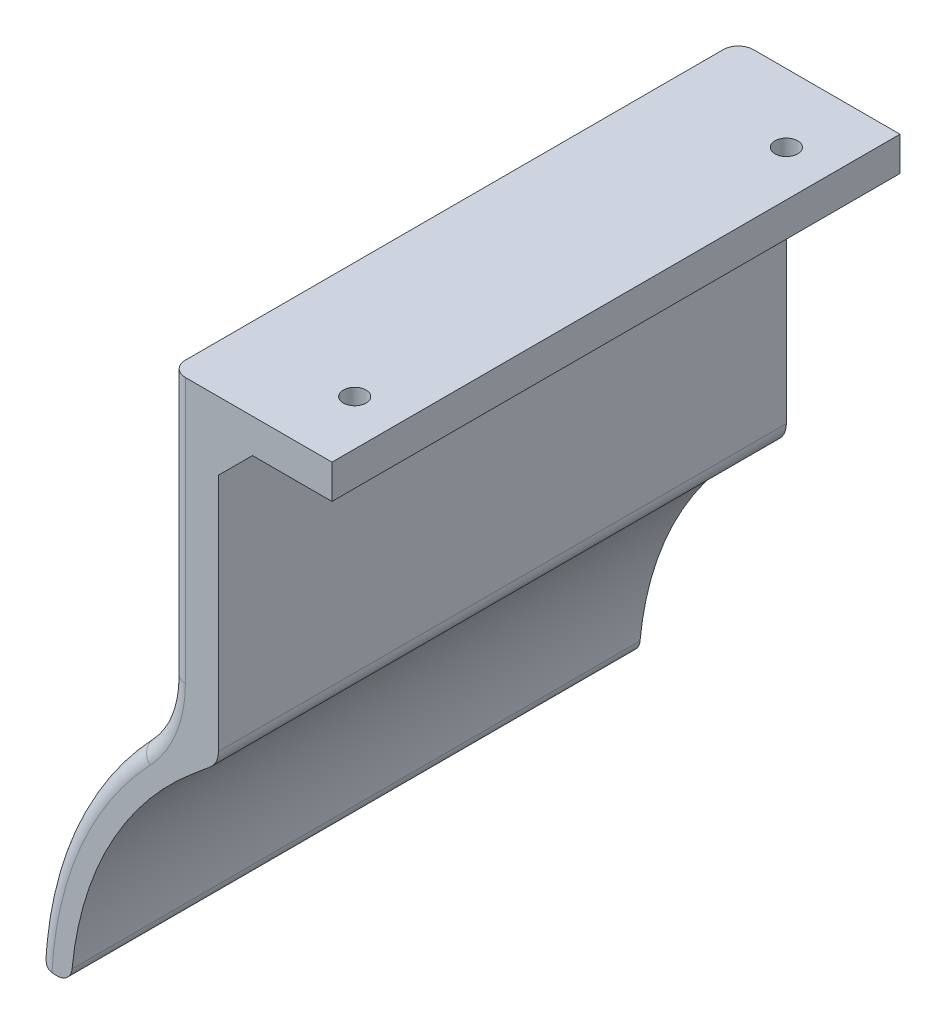
SolidWorks part; units mm, degrees
ref_plane "前视基准面" through (0, 0, 0) normal (0, 0, 1) x (1, 0, 0)
ref_plane "上视基准面" through (0, 0, 0) normal (0, 1, 0) x (1, 0, 0)
ref_plane "右视基准面" through (0, 0, 0) normal (1, 0, 0) x (0, 0, -1)
other "Configuration Table"
sketch "草图1" plane through (0, 0, 0) normal (0, 0, 1) x (1, 0, 0)
  line L1 (-30, 0) -> (0, 0) construction
  line L4 (-30, 0) -> (-33, 0)
  line L6 (0, 33) -> (-44.8073, 33) construction
  line L7 (-19.2836, 22.9813) -> (-16.9855, 24.9097)
  line L8 (-16.9855, 24.9097) -> (-16.9855, 39.9097)
  line L9 (-21.212, 25.2795) -> (-21.212, 39.9097)
  line L10 (-21.212, 39.9097) -> (-28.212, 39.9097)
  line L11 (-28.212, 39.9097) -> (-28.212, 42.9097)
  line L12 (-28.212, 42.9097) -> (-16.9855, 42.9097)
  line L13 (-16.9855, 42.9097) -> (-16.9855, 39.9097)
  line L14 (-21.212, 25.2795) -> (-16.9855, 24.9097)
  arc A0 (-30, 0) -> (-19.2836, 22.9813) centre (0, 0) cw
  arc A1 (-33, 0) -> (-21.212, 25.2795) centre (0, 0) cw
  arc A2 (-19.2836, 22.9813) -> (0, 30) centre (0, 0) cw construction
  arc A3 (-21.212, 25.2795) -> (0, 33) centre (0, 0) cw construction
  dimension "D1" = 30
  dimension "D4" = 33
  dimension "D6" = 50
  dimension "D2" = 50
  dimension "D3" = 3
  dimension "D5" = 3
  dimension "D7" = 15
  dimension "D8" = 7
  dimension "D9" = 3
extrude "凸台-拉伸1" add sketch "草图1" along normal mid plane 50 contours A1 L4 A0 L7 L14 region at (-27.2319, 13.4982, 0)
extrude "凸台-拉伸3" add sketch "草图1<7>" along normal mid plane 50 contours L9 L14 L8 L13 L12 L11 L10 region at (-20.3172, 35.6173, 0)
sketch "草图1<7>" plane through (0, 0, 0) normal (0, 0, 1) x (1, 0, 0) same geometry as "草图1"
ref_plane "基准面6" through (-16.9855, 0, 0) normal (1, 0, 0) x (0, 0, -1)
sketch "草图4" plane through (-16.9855, 0, 0) normal (1, 0, 0) x (0, 0, -1)
  line L0 (-25, 24.9097) -> (-16, 24.9097) construction
  line L1 (-25, 24.9097) -> (25, 24.9097) construction
  line L2 (25, 24.9097) -> (16, 24.9097) construction
  line L8 (-25, 42.9097) -> (25, 42.9097) construction
  line L9 (-16, 42.9097) -> (16, 42.9097)
  line L10 (-16, 42.9097) -> (-16, 27.9969)
  line L11 (-16, 27.9969) -> (16, 27.9969)
  line L12 (16, 42.9097) -> (16, 27.9969)
extrude "切除-拉伸1" cut sketch "草图4" against normal through all and the other way through all
fillet "圆角1" radius 10 1 edges at (-21.212, 25.2795, 0)
fillet "圆角17" radius 2 1 edges at (-16.9855, 24.9097, 0) type face fillet first side face at (-16.9855, 34.6815, 0) second side face at (-18.1346, 23.9455, 0)
sketch "草图5" plane through (0, 0, 0) normal (1, 0, 0) x (0, 0, -1)
  line L0 (-25, 0) -> (25, 0) construction
  line L3 (0, 0) -> (0, 22.9813) construction
  line L4 (-14, 9) -> (14, 9)
  line L5 (-14, 9) -> (-14, 16.4661)
  line L6 (-14, 16.4661) -> (14, 16.4661)
  line L7 (14, 9) -> (14, 16.4661)
  line L8 (-25, 22.9813) -> (25, 22.9813) construction
  line L9 (-25, 22.9813) -> (-25, 0) construction
  dimension "D1" = 28
  dimension "D2" = 16.4661
  dimension "D3" = 11
  dimension "D4" = 9
sketch "草图7" plane through (0, 0, 0) normal (0, 0, 1) x (1, 0, 0)
  line L0 (0, 0) -> (-33, 0)
  line L1 (-32.9548, 1.7271) -> (0, 0)
  arc A0 (-33, 0) -> (-32.9548, 1.7271) centre (0, 0) cw
  dimension "D1" = 3
extrude "切除-拉伸5" cut sketch "草图7" against normal through all both and the other way through all
sketch "草图9" plane through (0, 0, 0) normal (0, 0, 1) x (1, 0, 0)
  line L1 (-21.212, 39.9097) -> (-28.212, 39.9097)
  line L2 (-21.212, 39.9097) -> (-21.212, 42.9097)
  line L3 (-21.212, 42.9097) -> (-28.212, 42.9097)
  line L4 (-28.212, 39.9097) -> (-28.212, 42.9097)
extrude "切除-拉伸6" cut sketch "草图9" against normal through all both and the other way through all
ref_plane "基准面7" through (0, 42.9097, 0) normal (0, 1, 0) x (1, 0, 0)
sketch "草图10" plane through (0, 42.9097, 0) normal (0, 1, 0) x (1, 0, 0)
  line L0 (-16.9855, -13.2371) -> (-16.9855, 13.2371) construction
  line L1 (-21.212, 25) -> (-16.9855, 25)
  line L2 (-21.212, 25) -> (-21.212, 16)
  line L3 (-21.212, 16) -> (-16.9855, 16)
  line L4 (-16.9855, 25) -> (-16.9855, 16)
  line L5 (-21.212, 16) -> (-16.9855, 16) construction
  line L6 (-21.212, -25) -> (-16.9855, -25) construction
  line L7 (-21.212, -16) -> (-16.9855, -16)
  line L8 (-21.212, -16) -> (-21.212, -25)
  line L9 (-21.212, -25) -> (-16.9855, -25)
  line L10 (-16.9855, -16) -> (-16.9855, -25)
extrude "凸台-拉伸4" add sketch "草图10" along normal blind 10
sketch "草图12" plane through (-16.9855, 0, 0) normal (1, 0, 0) x (0, 0, -1)
  line L0 (25, 25.8423) -> (25, 52.9097) construction
  line L1 (-25, 52.9097) -> (25, 52.9097)
  line L2 (-25, 52.9097) -> (-25, 49.9097)
  line L3 (-25, 49.9097) -> (25, 49.9097)
  line L4 (25, 52.9097) -> (25, 49.9097)
  dimension "D1" = 3
extrude "凸台-拉伸6" add sketch "草图12" along normal blind 10 and the other way up to surface (4.2265 mm away) other way up to face at (-21.212, 41.2435, 20.5)
ref_plane "基准面8" through (0, 49.9097, 0) normal (0, -1, 0) x (-1, 0, 0)
sketch "草图14" plane through (0, 49.9097, 0) normal (0, -1, 0) x (-1, 0, 0)
  line L0 (6.9855, 25) -> (6.9855, 19) construction
  line L1 (6.9855, -25) -> (6.9855, 25) construction
  line L3 (6.9855, 19) -> (10.9855, 19) construction
  circle A0 centre (10.9855, 19) radius 1
  circle A1 centre (10.9855, -19) radius 1
  dimension "D3" = 2
  dimension "D1" = 6
  dimension "D2" = 4
extrude "切除-拉伸8" cut sketch "草图14" against normal through all
fillet "圆角50" radius 1.32 8 edges at (-30.3247, 13.0158, -25) (-21.9226, 25.8749, -25) (-30.3247, 13.0158, 25) (-21.9226, 25.8749, 25) (-21.212, 41.2435, -25) (-21.212, 41.2435, 25) (-29.9589, 1.5701, 0) (-32.9548, 1.7271, 0)
sketch "草图16" plane through (-16.9855, 0, 0) normal (1, 0, 0) x (0, 0, -1)
  line L1 (-16, 27.9969) -> (16, 27.9969)
  line L2 (-16, 27.9969) -> (-16, 49.9097)
  line L3 (-16, 49.9097) -> (16, 49.9097)
  line L4 (16, 27.9969) -> (16, 49.9097)
extrude "凸台-拉伸7" add sketch "草图16" against normal up to surface (4.2265 mm away) up to face at (-21.212, 40.4935, 0)
sketch "草图17" plane through (0, 0, -16) normal (0, 0, 1) x (1, 0, 0)
  line L2 (-21.3376, 27.9969) -> (-21.212, 27.9969)
  line L3 (-21.212, 27.9969) -> (-21.212, 29.5772)
  line L4 (-21.3376, 27.9969) -> (-21.212, 27.9969)
  line L5 (-21.212, 27.9969) -> (-21.212, 29.5772)
  arc A1 (-21.3376, 27.9969) -> (-21.212, 29.5772) centre (-31.212, 29.5772) ccw
  arc A2 (-21.3376, 27.9969) -> (-21.212, 29.5772) centre (-31.212, 29.5772) ccw
  dimension "D1" = 0
extrude "凸台-拉伸8" add sketch "草图17" along normal up to surface (32 mm away) up to face at (-21.2434, 28.5229, 16)
chamfer "倒角1" distance 3 angle 45 1 edges at (-16.9855, 49.9097, 0)
